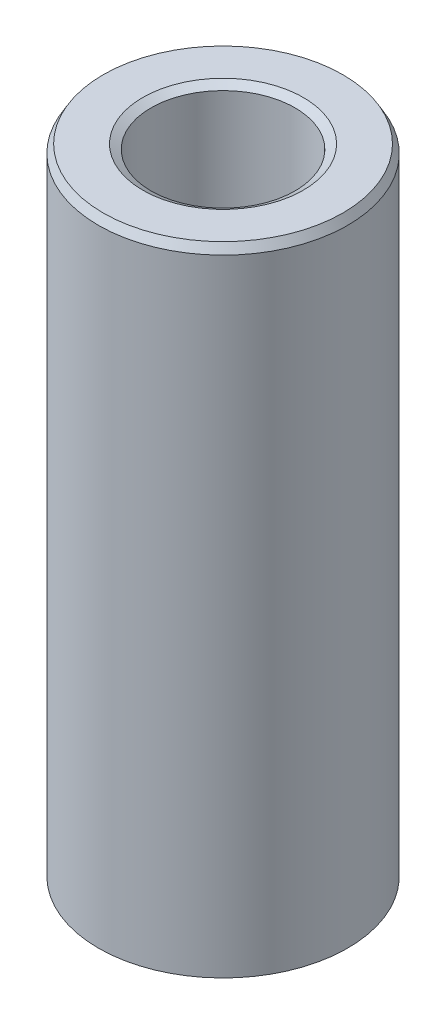
SolidWorks part; units mm, degrees
ref_plane "Front Plane" through (0, 0, 0) normal (0, 0, 1) x (1, 0, 0)
ref_plane "Top Plane" through (0, 0, 0) normal (0, 1, 0) x (1, 0, 0)
ref_plane "Right Plane" through (0, 0, 0) normal (1, 0, 0) x (0, 0, -1)
sketch "Sketch1" plane through (0, 0, 0) normal (0, 1, 0) x (1, 0, 0)
  circle A0 centre (0, 0) radius 17.5
  dimension "SLEEVE_OD" = 35
extrude "Boss-Extrude1" add sketch "Sketch1" along normal blind 89.7518
sketch "Sketch2" plane through (0, 0, 0) normal (0, 1, 0) x (1, 0, 0)
  circle A0 centre (0, 0) radius 10.1151
  dimension "BORE_D" = 20.2302
extrude "Cut-Extrude1" cut sketch "Sketch2" along normal through all
chamfer "Chamfer1" distance 1.1654 angle 30 4 edges at (0, 89.7518, 10.1151) (0, 0, 10.1151) (0, 0, 17.5) (0, 89.7518, 17.5) first distance on face at (0, 89.7518, 10.1151) first distance on face at (0, 0, 10.1151) first distance on face at (0, 89.7518, 17.5)
